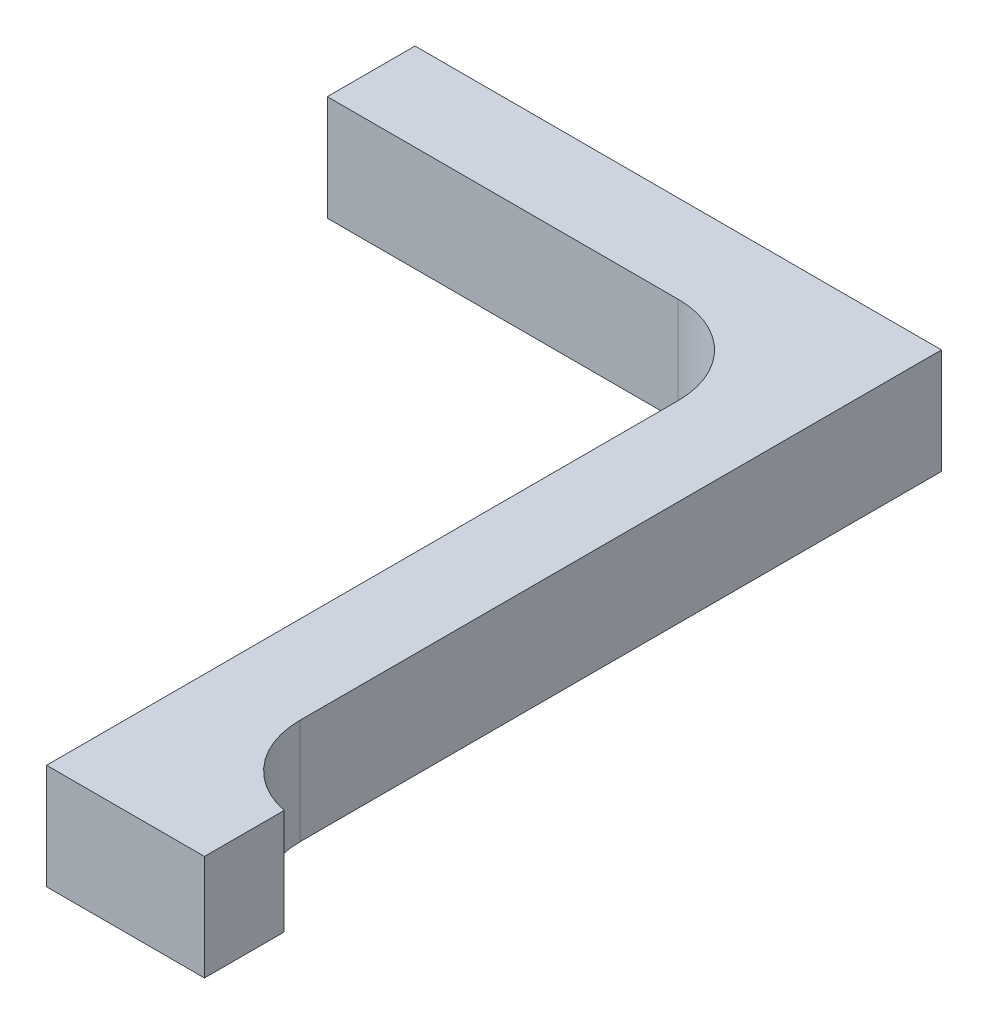
SolidWorks part; units mm, degrees
ref_plane "Ön Düzlem" through (0, 0, 0) normal (0, 0, 1) x (1, 0, 0)
ref_plane "Üst Düzlem" through (0, 0, 0) normal (0, 1, 0) x (1, 0, 0)
ref_plane "Sağ Düzlem" through (0, 0, 0) normal (1, 0, 0) x (0, 0, -1)
sketch "Sketch1" plane through (0, 0, 0) normal (0, 1, 0) x (1, 0, 0)
  line L0 (0, 0) -> (60, 0)
  line L1 (60, 0) -> (60, -92)
  line L2 (60, -92) -> (50, -92)
  line L3 (50, -92) -> (50, -10)
  line L4 (50, -10) -> (0, -10)
  line L5 (0, -10) -> (0, 0)
  dimension "D1" = 50
  dimension "D2" = 92
  dimension "D3" = 10
  dimension "D4" = 10
extrude "Boss-Extrude1" add sketch "Sketch1" along normal blind 12
sketch "Sketch2" plane through (60, 0, 0) normal (1, 0, 0) x (0, 0, -1)
  line L0 (-92, 0) -> (0, 0) construction
  line L1 (-92, 12) -> (-82.9217, 12)
  line L2 (-92, 12) -> (-92, 0)
  line L3 (-92, 0) -> (-82.9217, 0)
  line L4 (-82.9217, 12) -> (-82.9217, 0)
extrude "Boss-Extrude2" add sketch "Sketch2" along normal blind 8
fillet "Fillet1" radius 10 2 edges at (60, 6, 82.9217) (50, 6, 10)
